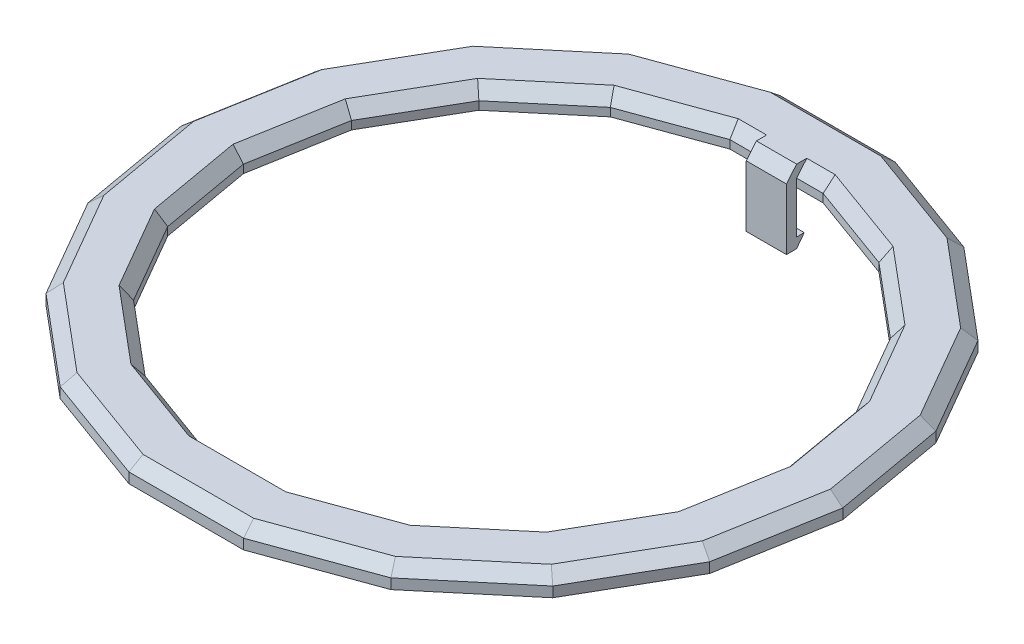
SolidWorks part; units mm, degrees
note: The reader was unsure of these and kept them because the rebuilt part matched: shared geometry of "Sketch1<7>".
ref_plane "Front Plane" through (0, 0, 0) normal (0, 0, 1) x (1, 0, 0)
ref_plane "Top Plane" through (0, 0, 0) normal (0, 1, 0) x (1, 0, 0)
ref_plane "Right Plane" through (0, 0, 0) normal (1, 0, 0) x (0, 0, -1)
sketch "Sketch1" plane through (0, 0, 0) normal (0, 1, 0) x (1, 0, 0)
  line L1 (65, 0) -> (61.08, 22.2313)
  line L2 (61.08, 22.2313) -> (49.7929, 41.7812)
  line L3 (49.7929, 41.7812) -> (32.5, 56.2917)
  line L4 (32.5, 56.2917) -> (11.2871, 64.0125)
  line L5 (11.2871, 64.0125) -> (-11.2871, 64.0125)
  line L6 (-11.2871, 64.0125) -> (-32.5, 56.2917)
  line L7 (-32.5, 56.2917) -> (-49.7929, 41.7812)
  line L8 (-49.7929, 41.7812) -> (-61.08, 22.2313)
  line L9 (-61.08, 22.2313) -> (-65, 0)
  line L10 (-65, 0) -> (-61.08, -22.2313)
  line L11 (-61.08, -22.2313) -> (-49.7929, -41.7812)
  line L12 (-49.7929, -41.7812) -> (-32.5, -56.2917)
  line L13 (-32.5, -56.2917) -> (-11.2871, -64.0125)
  line L14 (-11.2871, -64.0125) -> (11.2871, -64.0125)
  line L15 (11.2871, -64.0125) -> (32.5, -56.2917)
  line L16 (32.5, -56.2917) -> (49.7929, -41.7812)
  line L17 (49.7929, -41.7812) -> (61.08, -22.2313)
  line L18 (61.08, -22.2313) -> (65, 0)
  line L19 (62.9691, 0) -> (59.1716, 21.5367)
  line L20 (59.1716, 21.5367) -> (48.2372, 40.4758)
  line L21 (48.2372, 40.4758) -> (31.4846, 54.5329)
  line L22 (31.4846, 54.5329) -> (10.9345, 62.0125)
  line L23 (10.9345, 62.0125) -> (-10.9345, 62.0125)
  line L24 (-10.9345, 62.0125) -> (-31.4846, 54.5329)
  line L25 (-31.4846, 54.5329) -> (-48.2372, 40.4758)
  line L26 (-48.2372, 40.4758) -> (-59.1716, 21.5367)
  line L27 (-59.1716, 21.5367) -> (-62.9691, 0)
  line L28 (-62.9691, 0) -> (-59.1716, -21.5367)
  line L29 (-59.1716, -21.5367) -> (-48.2372, -40.4758)
  line L30 (-48.2372, -40.4758) -> (-31.4846, -54.5329)
  line L31 (-31.4846, -54.5329) -> (-10.9345, -62.0125)
  line L32 (-10.9345, -62.0125) -> (10.9345, -62.0125)
  line L33 (10.9345, -62.0125) -> (31.4846, -54.5329)
  line L34 (31.4846, -54.5329) -> (48.2372, -40.4758)
  line L35 (48.2372, -40.4758) -> (59.1716, -21.5367)
  line L36 (59.1716, -21.5367) -> (62.9691, 0)
  circle A0 centre (0, 0) radius 64.0125 construction
  circle A1 centre (0, 0) radius 62.0125 construction
  point P1 (0, 64.0125)
  dimension "D1" = 130
  dimension "D2" = 2
extrude "Boss-Extrude1" add sketch "Sketch1" against normal blind 1 contours L19 L20 L21 L22 L23 L24 L25 L26 L27 L28 L29 L30 L31 L32 L33 L34 L35 L36
extrude "Boss-Extrude3" add sketch "Sketch1<7>" against normal blind 4 separate body
sketch "Sketch1<7>" plane through (0, 0, 0) normal (0, 1, 0) x (1, 0, 0) same geometry as "Sketch1"
sketch "Sketch3" plane through (0, 0, 0) normal (0, 1, 0) x (1, 0, 0)
  line L1 (54.8149, 0) -> (51.5091, 18.7478)
  line L2 (51.5091, 18.7478) -> (41.9906, 35.2343)
  line L3 (41.9906, 35.2343) -> (27.4074, 47.4711)
  line L4 (27.4074, 47.4711) -> (9.5185, 53.9821)
  line L5 (9.5185, 53.9821) -> (-9.5185, 53.9821)
  line L6 (-9.5185, 53.9821) -> (-27.4074, 47.4711)
  line L7 (-27.4074, 47.4711) -> (-41.9906, 35.2343)
  line L8 (-41.9906, 35.2343) -> (-51.5091, 18.7478)
  line L9 (-51.5091, 18.7478) -> (-54.8149, 0)
  line L10 (-54.8149, 0) -> (-51.5091, -18.7478)
  line L11 (-51.5091, -18.7478) -> (-41.9906, -35.2343)
  line L12 (-41.9906, -35.2343) -> (-27.4074, -47.4711)
  line L13 (-27.4074, -47.4711) -> (-9.5185, -53.9821)
  line L14 (-9.5185, -53.9821) -> (9.5185, -53.9821)
  line L15 (9.5185, -53.9821) -> (27.4074, -47.4711)
  line L16 (27.4074, -47.4711) -> (41.9906, -35.2343)
  line L17 (41.9906, -35.2343) -> (51.5091, -18.7478)
  line L18 (51.5091, -18.7478) -> (54.8149, 0)
  circle A0 centre (0, 0) radius 53.9821 construction
  dimension "D1" = 109.6298
extrude "Cut-Extrude2" cut sketch "Sketch3" against normal up to surface (1 mm away) up to face at (0, -1, 0)
sketch "Sketch5" plane through (0, 0, 0) normal (0, 1, 0) x (1, 0, 0)
  line L0 (10.9345, 62.0125) -> (-10.9345, 62.0125) construction
  line L1 (54.8149, 0) -> (51.5091, 18.7478)
  line L2 (51.5091, 18.7478) -> (41.9906, 35.2343)
  line L3 (41.9906, 35.2343) -> (27.4074, 47.4711)
  line L4 (27.4074, 47.4711) -> (9.5185, 53.9821)
  line L5 (9.5185, 53.9821) -> (-9.5185, 53.9821)
  line L6 (-9.5185, 53.9821) -> (-27.4074, 47.4711)
  line L7 (-27.4074, 47.4711) -> (-41.9906, 35.2343)
  line L8 (-41.9906, 35.2343) -> (-51.5091, 18.7478)
  line L9 (-51.5091, 18.7478) -> (-54.8149, 0)
  line L10 (-54.8149, 0) -> (-51.5091, -18.7478)
  line L11 (-51.5091, -18.7478) -> (-41.9906, -35.2343)
  line L12 (-41.9906, -35.2343) -> (-27.4074, -47.4711)
  line L13 (-27.4074, -47.4711) -> (-9.5185, -53.9821)
  line L14 (-9.5185, -53.9821) -> (9.5185, -53.9821)
  line L15 (9.5185, -53.9821) -> (27.4074, -47.4711)
  line L16 (27.4074, -47.4711) -> (41.9906, -35.2343)
  line L17 (41.9906, -35.2343) -> (51.5091, -18.7478)
  line L18 (51.5091, -18.7478) -> (54.8149, 0)
  line L19 (52.784, 0) -> (49.6008, 18.0532)
  line L20 (49.6008, 18.0532) -> (40.4349, 33.9289)
  line L21 (40.4349, 33.9289) -> (26.392, 45.7123)
  line L22 (26.392, 45.7123) -> (9.1659, 51.9821)
  line L23 (9.1659, 51.9821) -> (-9.1659, 51.9821)
  line L24 (-9.1659, 51.9821) -> (-26.392, 45.7123)
  line L25 (-26.392, 45.7123) -> (-40.4349, 33.9289)
  line L26 (-40.4349, 33.9289) -> (-49.6008, 18.0532)
  line L27 (-49.6008, 18.0532) -> (-52.784, 0)
  line L28 (-52.784, 0) -> (-49.6008, -18.0532)
  line L29 (-49.6008, -18.0532) -> (-40.4349, -33.9289)
  line L30 (-40.4349, -33.9289) -> (-26.392, -45.7123)
  line L31 (-26.392, -45.7123) -> (-9.1659, -51.9821)
  line L32 (-9.1659, -51.9821) -> (9.1659, -51.9821)
  line L33 (9.1659, -51.9821) -> (26.392, -45.7123)
  line L34 (26.392, -45.7123) -> (40.4349, -33.9289)
  line L35 (40.4349, -33.9289) -> (49.6008, -18.0532)
  line L36 (49.6008, -18.0532) -> (52.784, 0)
  circle A0 centre (0, 0) radius 53.9821 construction
  circle A1 centre (0, 0) radius 51.9821 construction
  dimension "D1" = 2
  dimension "D2" = 8.0304
extrude "Boss-Extrude5" add sketch "Sketch5" against normal up to surface (4 mm away) up to face at (0, -4, 0)
sketch "Sketch6" plane through (0, -4, 0) normal (0, -1, 0) x (1, 0, 0)
  line L0 (-5.25, 53.9821) -> (-5.25, 51.9821)
  line L1 (9.5185, 53.9821) -> (-9.5185, 53.9821) construction
  line L2 (9.1659, 51.9821) -> (-9.1659, 51.9821) construction
  line L3 (-5.25, 51.9821) -> (5.25, 51.9821)
  line L4 (5.25, 51.9821) -> (5.25, 53.9821)
  line L5 (5.25, 53.9821) -> (-5.25, 53.9821)
  dimension "D1" = 10.5
  dimension "D2" = 5.25
extrude "Cut-Extrude3" cut sketch "Sketch6" against normal blind 1.25
sketch "Sketch7" plane through (0, 0, -51.9821) normal (0, 0, 1) x (1, 0, 0)
  line L1 (9.1659, 0) -> (-9.1659, 0) construction
  line L5 (3.95, 0) -> (-3.95, 0)
  line L6 (-3.95, 0) -> (-3.95, -14.4)
  line L7 (-3.95, -14.4) -> (3.95, -14.4)
  line L8 (3.95, -14.4) -> (3.95, 0)
  point P1 (0, -14.4)
  dimension "D1" = 7.9
  dimension "D2" = 14.4
extrude "Boss-Extrude6" add sketch "Sketch7" along normal blind 2
chamfer "Chamfer1" distance 2 angle 50 36 edges at (55.4365, 0, 32.0063) (41.1464, 0, 49.0364) (21.8936, 0, 60.1521) (0, 0, 64.0125) (-21.8936, 0, 60.1521) (-41.1464, 0, 49.0364) (51.1924, 0, -9.0266) (45.0178, 0, -25.9911) (-55.4365, 0, 32.0063) (33.4135, 0, -39.8206) (17.7789, 0, -48.8472) (-17.7789, 0, -48.8472) (-33.4135, 0, -39.8206) (-45.0178, 0, -25.9911) (-51.1924, 0, -9.0266) (-51.1924, 0, 9.0266) (-63.04, 0, 11.1157) (-45.0178, 0, 25.9911) (-33.4135, 0, 39.8206) (-17.7789, 0, 48.8472) (0, 0, 51.9821) (17.7789, 0, 48.8472) (33.4135, 0, 39.8206) (45.0178, 0, 25.9911) (51.1924, 0, 9.0266) (-63.04, 0, -11.1157) (-55.4365, 0, -32.0063) (-41.1464, 0, -49.0364) (-21.8936, 0, -60.1521) (0, 0, -64.0125) (21.8936, 0, -60.1521) (41.1464, 0, -49.0364) (55.4365, 0, -32.0063) (63.04, 0, -11.1157) (63.04, 0, 11.1157) (0, 0, -49.9821)
sketch "Sketch9" plane through (-3.95, 0, 0) normal (-1, 0, 0) x (0, 0, 1)
  line L0 (-51.9821, -14.4) -> (-53.4821, -12.4)
  line L1 (-53.4821, -12.4) -> (-51.9821, -12.4)
  line L2 (-51.9821, -4) -> (-51.9821, -14.4) construction
  line L3 (-51.9821, -12.4) -> (-51.9821, -14.4)
  dimension "D1" = 1.5
  dimension "D2" = 2
extrude "Boss-Extrude7" add sketch "Sketch9" against normal up to surface (7.9 mm away) up to face at (3.95, -5.3667, -51.6964)
